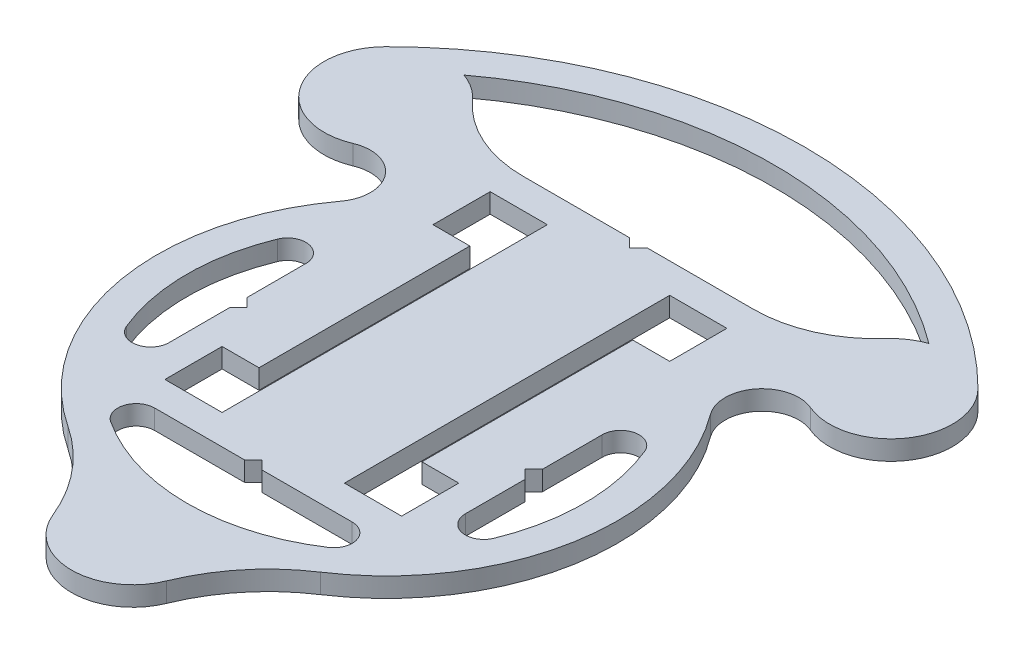
SolidWorks part; units mm, degrees
ref_plane "Front Plane" through (0, 0, 0) normal (0, 0, 1) x (1, 0, 0)
ref_plane "Top Plane" through (0, 0, 0) normal (0, 1, 0) x (1, 0, 0)
ref_plane "Right Plane" through (0, 0, 0) normal (1, 0, 0) x (0, 0, -1)
ref_plane "Plane1" through (0, 0, 26.3) normal (0, 0, 1) x (1, 0, 0)
ref_plane "Plane2" through (0, 0, 9.8) normal (0, 0, 1) x (1, 0, 0)
ref_axis "Axis1" through (0, 3.3337, 9.8) along (0, -1, 0)
sketch "Sketch1" plane through (0, 0, 0) normal (0, 1, 0) x (1, 0, 0)
  line L1 (-19.1, -26.3) -> (19.1, -26.3) construction
  line L2 (-19.1, -26.3) -> (-19.1, 26.3) construction
  line L4 (19.1, -26.3) -> (19.1, 26.3) construction
  line L5 (-19.1, -26.3) -> (19.1, 26.3) construction
  line L6 (-19.1, 26.3) -> (19.1, -26.3) construction
  line L10 (0, -9.8) -> (41.1, 31.3) construction
  line L19 (-19.1, 26.3) -> (19.1, 26.3) construction
  line L21 (0, -9.8) -> (-41.1, 31.3) construction
  line L22 (-41.1, 31.3) -> (41.1, 31.3) construction
  line L24 (0, -9.8) -> (0, 31.3) construction
  line L28 (41.1, 31.3) -> (48.1711, 38.3711) construction
  line L30 (24.1, -31.3) -> (24.1, 31.3) construction
  line L31 (-24.1, 31.3) -> (24.1, 31.3) construction
  line L32 (-24.1, -31.3) -> (-24.1, 31.3) construction
  line L33 (-24.1, -31.3) -> (24.1, -31.3) construction
  line L34 (0, -9.8) -> (0, -50.9) construction
  line L35 (-18.7393, 31.3) -> (18.7393, 31.3)
  line L36 (-19.1, -26.3) -> (-24.1, -31.3) construction
  line L38 (-24.1, -31.3) -> (-27.6405, -34.8405) construction
  line L40 (19.1, -26.3) -> (24.1, -31.3) construction
  line L42 (24.1, -31.3) -> (27.6405, -34.8405) construction
  line L43 (-24.1, -20.9298) -> (-24.1208, 1.6824)
  line L44 (24.1, -20.9298) -> (24.1, 1.3298)
  line L45 (-33.6464, -26.3) -> (-33.6464, 37.9667) construction
  line L46 (-33.6464, -26.3) -> (-19.1, -26.3) construction
  line L47 (-24.1, -22.6935) -> (-24.1, 6.3801) construction
  line L48 (-16.0634, -31.3) -> (16.0634, -31.3)
  circle A0 centre (-41.1, 31.3) radius 10 construction
  circle A1 centre (41.1, 31.3) radius 10 construction
  arc A2 (-48.1711, 38.3711) -> (48.1711, 38.3711) centre (0, -9.8) cw
  arc A3 (-37.814, 40.7447) -> (37.814, 40.7447) centre (0, -9.8) cw
  circle A4 centre (0, -50.9) radius 10 construction
  arc A5 (24.1, -31.3) -> (-24.1, -31.3) centre (0, -9.8) cw construction
  arc A7 (-33.6464, 37.9667) -> (-18.7393, 31.3) centre (-18.7393, 51.3) ccw
  arc A8 (18.7393, 31.3) -> (33.6464, 37.9667) centre (18.7393, 51.3) ccw
  arc A13 (-37.814, 40.7447) -> (-33.6464, 37.9667) centre (-41.1, 31.3) cw
  arc A14 (37.814, 40.7447) -> (33.6464, 37.9667) centre (41.1, 31.3) ccw
  arc A15 (27.6405, -34.8405) -> (-27.6405, -34.8405) centre (0, -9.8) cw construction
  arc A16 (9.2621, -54.6701) -> (20.5326, -40.9358) centre (37.0484, -65.9803) cw
  arc A17 (-20.5326, -40.9358) -> (-9.2621, -54.6701) centre (-37.0484, -65.9803) cw
  arc A24 (9.2621, -54.6701) -> (-9.2621, -54.6701) centre (0, -50.9) cw
  arc A26 (-37.1966, 22.0933) -> (-30.0379, 12.9916) centre (-34.8546, 16.5693) cw
  arc A27 (-30.0379, 12.9916) -> (-20.5326, -40.9358) centre (0.2124, -9.4778) ccw
  arc A28 (37.1966, 22.0933) -> (30.0379, 12.9916) centre (34.8546, 16.5693) ccw
  arc A29 (30.0379, 12.9916) -> (20.5326, -40.9358) centre (-0.2124, -9.4778) cw
  arc A30 (-24.1, 11.7) -> (24.1, 11.7) centre (0, -9.8) ccw construction
  arc A31 (-29.8751, 2.4695) -> (-24.1208, 1.6824) centre (-27.1, 1.3298) cw
  arc A32 (-24.1, -20.9298) -> (-29.8751, -22.0695) centre (-27.1, -20.9298) cw
  arc A33 (-17.7083, -36.8088) -> (-16.0634, -31.3) centre (-16.0634, -34.3) cw
  arc A34 (17.7083, -36.8088) -> (16.0634, -31.3) centre (16.0634, -34.3) ccw
  arc A35 (24.1, 1.3298) -> (29.8751, 2.4695) centre (27.1, 1.3298) cw
  arc A36 (29.8751, -22.0695) -> (24.1, -20.9298) centre (27.1, -20.9298) cw
  arc A37 (29.8751, 2.4695) -> (29.8751, -22.0695) centre (0, -9.8) cw
  arc A38 (-29.8751, -22.0695) -> (-29.8751, 2.4695) centre (0, -9.8) cw
  arc A39 (-17.7083, -36.8088) -> (17.7083, -36.8088) centre (0, -9.8) ccw
  arc A40 (-37.1966, 22.0933) -> (-48.1711, 38.3711) centre (-41.1, 31.3) cw
  arc A41 (37.1966, 22.0933) -> (48.1711, 38.3711) centre (41.1, 31.3) ccw
  point P0 (0, 0)
  point P59 (-26.6935, 4.3021)
  dimension "D5" = 5
  dimension "D8" = 30
  dimension "D9" = 3
  dimension "D10" = 6
  dimension "D3" = 20
  dimension "D4" = 5
  dimension "D6" = 20
  dimension "D7" = 5
  dimension "D1" = 38.2
  dimension "D2" = 52.6
extrude "Boss-Extrude1" add sketch "Sketch1" along normal blind 3.175
sketch "Sketch2" plane through (0, 3.175, 0) normal (0, 1, 0) x (1, 0, 0)
  line L0 (-10.1, 0) -> (10.1, 0) construction
  line L5 (-10.1, 26.3) -> (-10.1, -26.3) construction
  line L6 (10.1, 26.3) -> (10.1, -26.3) construction
  line L7 (-13.1, 17.3) -> (-13.1, -17.3) construction
  line L8 (13.1, 17.3) -> (13.1, -17.3) construction
  line L9 (-13.1, 0) -> (-10.1, 0) construction
  line L10 (10.1, 0) -> (13.1, 0) construction
  line L11 (-10.1, 26.3) -> (-19.1, 26.3) construction
  line L12 (-19.1, 26.3) -> (-19.1, 17.3) construction
  line L13 (-19.1, 17.3) -> (-13.1, 17.3) construction
  line L14 (-10.1, -26.3) -> (-19.1, -26.3) construction
  line L15 (-19.1, -26.3) -> (-19.1, -17.3) construction
  line L16 (-19.1, -17.3) -> (-13.1, -17.3) construction
  line L17 (10.1, 26.3) -> (19.1, 26.3) construction
  line L18 (19.1, 26.3) -> (19.1, 17.3) construction
  line L19 (19.1, 17.3) -> (13.1, 17.3) construction
  line L20 (10.1, -26.3) -> (19.1, -26.3) construction
  line L21 (19.1, -26.3) -> (19.1, -17.3) construction
  line L22 (19.1, -17.3) -> (13.1, -17.3) construction
  line L23 (-19.25, -17.15) -> (-13.25, -17.15)
  line L24 (-13.25, 17.15) -> (-13.25, -17.15)
  line L25 (-19.25, 17.15) -> (-13.25, 17.15)
  line L26 (-19.25, 26.45) -> (-19.25, 17.15)
  line L27 (-9.95, 26.45) -> (-19.25, 26.45)
  line L28 (-9.95, 26.45) -> (-9.95, -26.45)
  line L29 (-9.95, -26.45) -> (-19.25, -26.45)
  line L30 (-19.25, -26.45) -> (-19.25, -17.15)
  line L31 (19.25, -17.15) -> (13.25, -17.15)
  line L32 (13.25, 17.15) -> (13.25, -17.15)
  line L33 (19.25, 17.15) -> (13.25, 17.15)
  line L34 (19.25, 26.45) -> (19.25, 17.15)
  line L35 (9.95, 26.45) -> (19.25, 26.45)
  line L36 (9.95, 26.45) -> (9.95, -26.45)
  line L37 (9.95, -26.45) -> (19.25, -26.45)
  line L38 (19.25, -26.45) -> (19.25, -17.15)
  point P3 (0, 0)
  point P9 (-10.1, 0)
  point P12 (10.1, 0)
  point P15 (-13.1, 0)
  point P18 (13.1, 0)
  dimension "D1" = 20.2
  dimension "D2" = 52.6
  dimension "D3" = 3
  dimension "D4" = 34.6
  dimension "D5" = 9
  dimension "D6" = 0.15
  dimension "D7" = 0.15
extrude "Cut-Extrude3" cut sketch "Sketch2" against normal up to next
sketch "Sketch8" plane through (0, 3.175, 0) normal (0, 1, 0) x (1, 0, 0)
  line L0 (0, -9.8) -> (0, -31.3) construction
  line L1 (16.0634, -31.3) -> (-16.0634, -31.3) construction
  line L2 (0, -9.8) -> (-24.1104, -9.6237) construction
  line L3 (-24.1, -20.9298) -> (-24.1208, 1.6824) construction
  line L4 (0, -9.8) -> (24.1, -9.8) construction
  line L5 (24.1, 1.3298) -> (24.1, -20.9298) construction
  line L6 (0, -9.8) -> (0, 31.3) construction
  line L7 (-18.7393, 31.3) -> (18.7393, 31.3) construction
  line L8 (-22.702, -9.634) -> (-24.1117, -8.2152)
  line L9 (-24.1117, -8.2152) -> (-24.1091, -11.0321)
  line L10 (-24.1091, -11.0321) -> (-22.702, -9.634)
  line L11 (22.6858, -9.8) -> (24.1, -11.2142)
  line L12 (24.1, -11.2142) -> (24.1, -8.3858)
  line L13 (24.1, -8.3858) -> (22.6858, -9.8)
  line L14 (0, -29.8858) -> (-1.4142, -31.3)
  line L15 (-1.4142, -31.3) -> (1.4142, -31.3)
  line L16 (1.4142, -31.3) -> (0, -29.8858)
  line L17 (0, 29.8858) -> (-1.4142, 31.3)
  line L18 (-1.4142, 31.3) -> (1.4142, 31.3)
  line L19 (1.4142, 31.3) -> (0, 29.8858)
  point P16 (-24.1104, -9.6237)
  point P20 (24.1, -9.8)
  point P24 (0, -31.3)
  point P28 (0, 31.3)
  point P30 (0, 27.8177)
  dimension "D1" = 2
extrude "Cut-Extrude4" cut sketch "Sketch8" against normal up to next
sketch "Sketch9" plane through (0, 3.175, 0) normal (0, 1, 0) x (1, 0, 0)
  line L1 (-48.1711, 38.3711) -> (-44.6355, 34.8355)
  line L2 (-34.0621, 49.1973) -> (-31.5621, 44.8671)
  line L3 (-17.6318, 56.0029) -> (-16.3377, 51.1733)
  line L4 (0, 58.3242) -> (0, 53.3242)
  line L5 (17.6318, 56.0029) -> (16.3377, 51.1733)
  line L6 (34.0621, 49.1973) -> (31.5621, 44.8671)
  line L7 (48.1711, 38.3711) -> (44.6355, 34.8355)
  line L8 (-48.1711, 38.3711) -> (-46.4033, 36.6033)
  line L9 (-43.7894, 42.3861) -> (-42.1824, 40.471)
  line L10 (-39.0744, 46.0041) -> (-37.6405, 43.9562)
  line L11 (-34.0621, 49.1973) -> (-32.8121, 47.0322)
  line L12 (-28.7905, 51.9415) -> (-27.734, 49.6757)
  line L13 (-23.2998, 54.2158) -> (-22.4448, 51.8666)
  line L14 (-17.6318, 56.0029) -> (-16.9848, 53.5881)
  line L15 (-11.8296, 57.2892) -> (-11.3955, 54.8272)
  line L16 (-5.9374, 58.0649) -> (-5.7195, 55.5745)
  line L17 (0, 58.3242) -> (0, 55.8242)
  line L18 (5.9374, 58.0649) -> (5.7195, 55.5745)
  line L19 (11.8296, 57.2892) -> (11.3955, 54.8272)
  line L20 (17.6318, 56.0029) -> (16.9848, 53.5881)
  line L21 (23.2998, 54.2158) -> (22.4448, 51.8666)
  line L22 (28.7905, 51.9415) -> (27.734, 49.6757)
  line L23 (34.0621, 49.1973) -> (32.8121, 47.0322)
  line L24 (39.0744, 46.0041) -> (37.6405, 43.9562)
  line L25 (43.7894, 42.3861) -> (42.1824, 40.471)
  line L26 (48.1711, 38.3711) -> (46.4033, 36.6033)
  line L27 (-48.1711, 38.3711) -> (-47.2872, 37.4872)
  line L28 (-47.323, 39.2044) -> (-46.4547, 38.3053)
  line L29 (-46.4606, 40.0229) -> (-45.6081, 39.1087)
  line L30 (-45.584, 40.8261) -> (-44.7476, 39.8972)
  line L31 (-44.6935, 41.614) -> (-43.8734, 40.6706)
  line L32 (-43.7894, 42.3861) -> (-42.9859, 41.4286)
  line L33 (-42.8719, 43.1424) -> (-42.0853, 42.171)
  line L34 (-41.9414, 43.8826) -> (-41.1719, 42.8976)
  line L35 (-40.9982, 44.6064) -> (-40.2459, 43.6081)
  line L36 (-40.0424, 45.3136) -> (-39.3077, 44.3023)
  line L37 (-39.0744, 46.0041) -> (-38.3575, 44.9801)
  line L38 (-38.0946, 46.6775) -> (-37.3956, 45.6412)
  line L39 (-37.1031, 47.3337) -> (-36.4223, 46.2854)
  line L40 (-36.1003, 47.9726) -> (-35.4379, 46.9125)
  line L41 (-35.0865, 48.5938) -> (-34.4427, 47.5224)
  line L42 (-34.0621, 49.1973) -> (-33.4371, 48.1147)
  line L43 (-33.0273, 49.7827) -> (-32.4212, 48.6895)
  line L44 (-31.9824, 50.3501) -> (-31.3955, 49.2464)
  line L45 (-30.9277, 50.8991) -> (-30.3602, 49.7853)
  line L46 (-29.8637, 51.4296) -> (-29.3157, 50.3061)
  line L47 (-28.7905, 51.9415) -> (-28.2622, 50.8086)
  line L48 (-27.7086, 52.4345) -> (-27.2002, 51.2926)
  line L49 (-26.6182, 52.9086) -> (-26.1298, 51.758)
  line L50 (-25.5198, 53.3636) -> (-25.0515, 52.2047)
  line L51 (-24.4135, 53.7994) -> (-23.9656, 52.6324)
  line L52 (-23.2998, 54.2158) -> (-22.8723, 53.0412)
  line L53 (-22.1791, 54.6127) -> (-21.7721, 53.4308)
  line L54 (-21.0515, 54.9899) -> (-20.6653, 53.8011)
  line L55 (-19.9176, 55.3475) -> (-19.5521, 54.1521)
  line L56 (-18.7776, 55.6852) -> (-18.433, 54.4836)
  line L57 (-17.6318, 56.0029) -> (-17.3083, 54.7955)
  line L58 (-16.4807, 56.3006) -> (-16.1783, 55.0877)
  line L59 (-15.3246, 56.5782) -> (-15.0434, 55.3602)
  line L60 (-14.1638, 56.8355) -> (-13.9039, 55.6128)
  line L61 (-12.9987, 57.0725) -> (-12.7602, 55.8455)
  line L62 (-11.8296, 57.2892) -> (-11.6126, 56.0582)
  line L63 (-10.657, 57.4855) -> (-10.4614, 56.2508)
  line L64 (-9.4811, 57.6612) -> (-9.3071, 56.4234)
  line L65 (-8.3022, 57.8164) -> (-8.1499, 56.5757)
  line L66 (-7.1209, 57.951) -> (-6.9903, 56.7078)
  line L67 (-5.9374, 58.0649) -> (-5.8285, 56.8197)
  line L68 (-4.7521, 58.1582) -> (-4.6649, 56.9113)
  line L69 (-3.5653, 58.2308) -> (-3.4999, 56.9825)
  line L70 (-2.3775, 58.2827) -> (-2.3339, 57.0334)
  line L71 (-1.1889, 58.3138) -> (-1.1671, 57.064)
  line L72 (0, 58.3242) -> (0, 57.0742)
  line L73 (1.1889, 58.3138) -> (1.1671, 57.064)
  line L74 (2.3775, 58.2827) -> (2.3339, 57.0334)
  line L75 (3.5653, 58.2308) -> (3.4999, 56.9825)
  line L76 (4.7521, 58.1582) -> (4.6649, 56.9113)
  line L77 (5.9374, 58.0649) -> (5.8285, 56.8197)
  line L78 (7.1209, 57.951) -> (6.9903, 56.7078)
  line L79 (8.3022, 57.8164) -> (8.1499, 56.5757)
  line L80 (9.4811, 57.6612) -> (9.3071, 56.4234)
  line L81 (10.657, 57.4855) -> (10.4614, 56.2508)
  line L82 (11.8296, 57.2892) -> (11.6126, 56.0582)
  line L83 (12.9987, 57.0725) -> (12.7602, 55.8455)
  line L84 (14.1638, 56.8355) -> (13.9039, 55.6128)
  line L85 (15.3246, 56.5782) -> (15.0434, 55.3602)
  line L86 (16.4807, 56.3006) -> (16.1783, 55.0877)
  line L87 (17.6318, 56.0029) -> (17.3083, 54.7955)
  line L88 (18.7776, 55.6852) -> (18.433, 54.4836)
  line L89 (19.9176, 55.3475) -> (19.5521, 54.1521)
  line L90 (21.0515, 54.9899) -> (20.6653, 53.8011)
  line L91 (22.1791, 54.6127) -> (21.7721, 53.4308)
  line L92 (23.2998, 54.2158) -> (22.8723, 53.0412)
  line L93 (24.4135, 53.7994) -> (23.9656, 52.6324)
  line L94 (25.5198, 53.3636) -> (25.0515, 52.2047)
  line L95 (26.6182, 52.9086) -> (26.1298, 51.758)
  line L96 (27.7086, 52.4345) -> (27.2002, 51.2926)
  line L97 (28.7905, 51.9415) -> (28.2622, 50.8086)
  line L98 (29.8637, 51.4296) -> (29.3157, 50.3061)
  line L99 (30.9277, 50.8991) -> (30.3602, 49.7853)
  line L100 (31.9824, 50.3501) -> (31.3955, 49.2464)
  line L101 (33.0273, 49.7827) -> (32.4212, 48.6895)
  line L102 (34.0621, 49.1973) -> (33.4371, 48.1147)
  line L103 (35.0865, 48.5938) -> (34.4427, 47.5224)
  line L104 (36.1003, 47.9726) -> (35.4379, 46.9125)
  line L105 (37.1031, 47.3337) -> (36.4223, 46.2854)
  line L106 (38.0946, 46.6775) -> (37.3956, 45.6412)
  line L107 (39.0744, 46.0041) -> (38.3575, 44.9801)
  line L108 (40.0424, 45.3136) -> (39.3077, 44.3023)
  line L109 (40.9982, 44.6064) -> (40.2459, 43.6081)
  line L110 (41.9414, 43.8826) -> (41.1719, 42.8976)
  line L111 (42.8719, 43.1424) -> (42.0853, 42.171)
  line L112 (43.7894, 42.3861) -> (42.9859, 41.4286)
  line L113 (44.6935, 41.614) -> (43.8734, 40.6706)
  line L114 (45.584, 40.8261) -> (44.7476, 39.8972)
  line L115 (46.4606, 40.0229) -> (45.6081, 39.1087)
  line L116 (47.323, 39.2044) -> (46.4547, 38.3053)
  line L117 (48.1711, 38.3711) -> (47.2872, 37.4872)
  point P0 (0, 0)
  dimension "D1" = 5
  dimension "D3" = 2.5
  dimension "D5" = 1.25
  dimension "D2" = 7
  dimension "D4" = 19
  dimension "D6" = 91
equation "\"D7@Sketch2\"=\"D6@Sketch2\""
